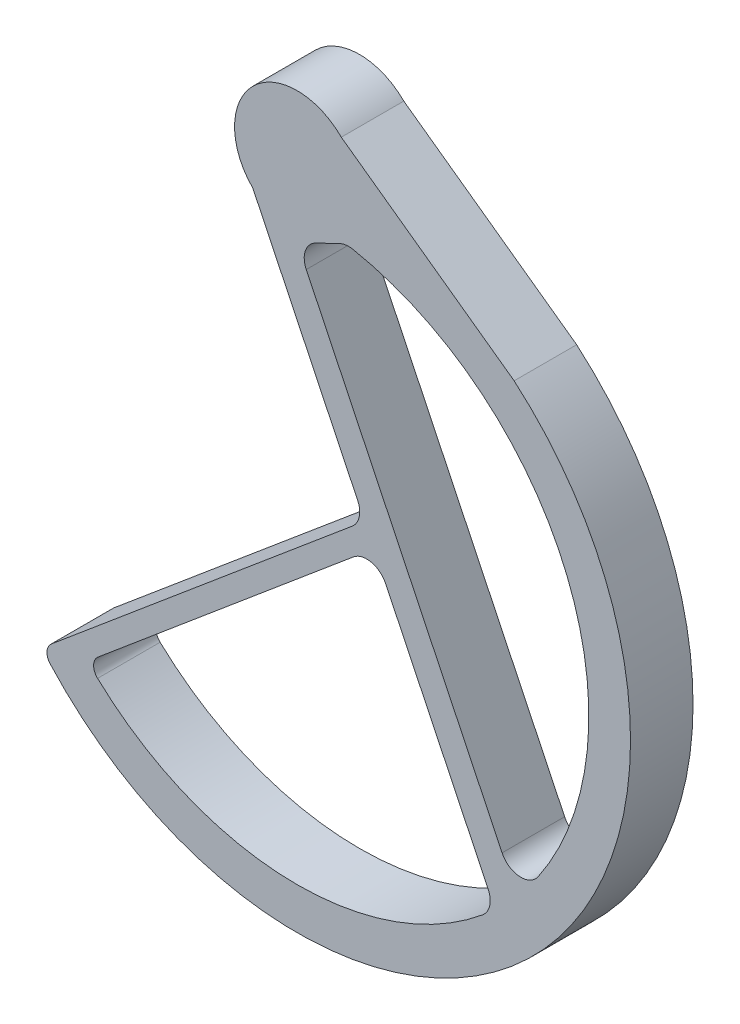
SolidWorks part; units mm, degrees
ref_plane "正面" through (0, 0, 0) normal (0, 0, 1) x (1, 0, 0)
ref_plane "平面" through (0, 0, 0) normal (0, 1, 0) x (1, 0, 0)
ref_plane "右側面" through (0, 0, 0) normal (1, 0, 0) x (0, 0, -1)
sketch "ｽｹｯﾁ4" plane through (0, 0, 0) normal (0, 0, 1) x (1, 0, 0)
  line L0 (0, 0.7897) -> (0, 0)
  line L1 (-53.6231, -124.9951) -> (-58.9406, -129.4571)
  line L3 (-10.6066, -10.6066) -> (14.5363, -62.8896)
  line L4 (-53.6231, -124.9951) -> (13.2442, -68.8868)
  line L5 (21.2324, -76.8138) -> (45.8448, -127.9938)
  line L6 (10.6066, 10.6066) -> (52.0762, -19.2705)
  line L7 (-58.0696, -135.2532) -> (-57.9498, -135.1527)
  line L8 (-47.7477, -126.5866) -> (13.5112, -75.1515)
  arc A1 (-59.2335, -133.7716) -> (52.0762, -19.2705) centre (0, -80) ccw
  arc A2 (-47.8702, -131.073) -> (44.5187, -134.0193) centre (0, -80) ccw
  arc A3 (10.6066, 10.6066) -> (-10.6066, -10.6066) centre (0, 0) ccw
  arc A4 (-59.2335, -133.7716) -> (-58.9406, -129.4571) centre (-57.0123, -131.7552) cw
  arc A5 (-47.8702, -131.073) -> (-47.7477, -126.5866) centre (-45.8186, -128.8841) cw
  arc A6 (13.5112, -75.1515) -> (21.2324, -76.8138) centre (16.7264, -78.9807) cw
  arc A7 (13.2442, -68.8868) -> (14.5363, -62.8896) centre (10.0302, -65.0566) ccw
  arc A8 (45.8448, -127.9938) -> (44.5187, -134.0193) centre (41.3388, -130.1608) cw
  point P18 (-61.2836, -131.423)
  point P21 (-50.2744, -128.7081)
  point P24 (18.4421, -71.0114)
  dimension "D3" = 140
  dimension "D4" = 30
  dimension "D5" = 5
  dimension "D6" = 3
  dimension "D7" = 3
  dimension "D8" = 5
  dimension "D9" = 5
  dimension "D10" = 5
  dimension "D2" = 5
extrude "ﾎﾞｽ - 押し出し1" add sketch "ｽｹｯﾁ4" along normal blind 15 contours A7 L4 L1 A4 A1 L6 A3 L3 L5 A8 A2 A5 L8 A6 region at (29.7837, -70.5076, 0)
sketch "ｽｹｯﾁ6" plane through (0, 0, 15) normal (0, 0, 1) x (1, 0, 0)
  line L6 (49.1896, -118.7973) -> (2.2018, -21.089)
  line L7 (6.4834, -13.4819) -> (4.5408, -14.416)
  line L8 (6.4834, -13.4819) -> (10.2197, -11.6851)
  arc A0 (57.8261, -119.448) -> (13.3394, -11.2828) centre (0, -80) ccw
  arc A1 (2.2018, -21.089) -> (4.5408, -14.416) centre (6.7078, -18.9221) cw
  arc A2 (13.3394, -11.2828) -> (10.2197, -11.6851) centre (12.3866, -16.1911) ccw
  arc A3 (57.8261, -119.448) -> (49.1896, -118.7973) centre (53.6956, -116.6303) cw
  point P7 (0.0348, -16.583)
  point P14 (52.6925, -126.0814)
  dimension "D3" = 121.502
  dimension "D4" = 70
  dimension "D1" = 5
  dimension "D2" = 5
  dimension "D5" = 5
  dimension "D6" = 90
extrude "ｶｯﾄ - 押し出し1" cut sketch "ｽｹｯﾁ6" against normal blind 15
sketch "ｽｹｯﾁ8" plane through (0, 0, 0) normal (0, 0, -1) x (-1, 0, 0)
  circle A0 centre (0, 0) radius 10.1
extrude "ｶｯﾄ - 押し出し3" cut sketch "ｽｹｯﾁ8" against normal blind 2
